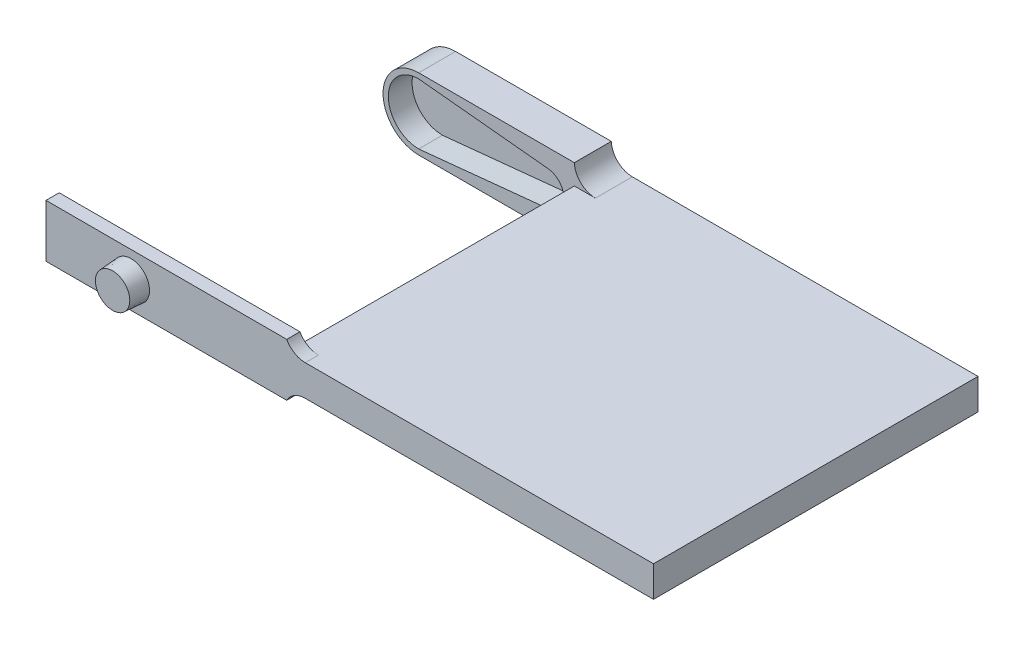
SolidWorks part; units mm, degrees
ref_plane "Front Plane" through (0, 0, 0) normal (0, 0, 1) x (1, 0, 0)
ref_plane "Top Plane" through (0, 0, 0) normal (0, 1, 0) x (1, 0, 0)
ref_plane "Right Plane" through (0, 0, 0) normal (1, 0, 0) x (0, 0, -1)
ref_plane "Ground Plane" through (0, 0, 29.25) normal (0, 0, -1) x (-1, 0, 0)
sketch "Sketch1" plane through (0, 0, 0) normal (0, 0, 1) x (1, 0, 0)
  line L0 (0, 3.375) -> (-13.75, 3.375) construction
  line L1 (0, 3.375) -> (0, 6.25) construction
  line L2 (-12.2651, 5.0167) -> (0, 6.25)
  line L3 (-13.75, 3.375) -> (-13.75, 1.1142) construction
  line L4 (-12.2651, 1.7333) -> (0, 0.5)
  line L5 (12.2651, 1.7333) -> (0, 0.5)
  line L6 (12.2651, 5.0167) -> (0, 6.25)
  line L7 (-2.875, 3.375) -> (-2.875, -5.5898) construction
  line L8 (-14.75, 0) -> (14.75, 0)
  line L9 (-14.75, 0) -> (-14.75, 6.75)
  line L10 (-14.75, 6.75) -> (14.75, 6.75)
  line L11 (-43.5503, 24.4221) -> (7.9447, 11.3967) construction
  line L12 (13.75, 3.375) -> (13.75, 0.9067) construction
  line L13 (14.75, 4.8371) -> (49.5, 4.8371)
  line L14 (14.5, 4.8371) -> (14.5, 1.9129) construction
  line L15 (14.75, 1.9129) -> (49.5, 1.9129)
  line L16 (49.5, 4.8371) -> (49.5, 1.9129)
  line L17 (-43.5503, 24.4221) -> (7.9447, 11.3967)
  line L18 (14.75, 6.75) -> (14.75, 0)
  line L19 (8.1899, 12.3661) -> (3.8863, -4.648) construction
  line L20 (8.1899, 12.3661) -> (3.8863, -4.648)
  line L21 (8.1899, 12.3661) -> (3.8863, -4.648)
  line L22 (8.1899, 12.3661) -> (3.8863, -4.648) construction
  line L23 (8.1899, 12.3661) -> (3.8863, -4.648)
  circle A0 centre (0, 3.375) radius 2.875 construction
  arc A1 (-12.2651, 5.0167) -> (-12.2651, 1.7333) centre (-12.1, 3.375) ccw
  arc A2 (12.2651, 5.0167) -> (12.2651, 1.7333) centre (12.1, 3.375) cw
  circle A3 centre (-12.1, 3.375) radius 0.2914
  circle A4 centre (-10.0632, 3.375) radius 0.2914
  circle A5 centre (-8.0264, 3.375) radius 0.2914
  circle A6 centre (8.0264, 3.375) radius 0.2914
  circle A7 centre (10.0632, 3.375) radius 0.2914
  circle A8 centre (12.1, 3.375) radius 0.2914
  arc A9 (0, 6.75) -> (0, 0) centre (0, 3.375) ccw
  arc A10 (0, 6.25) -> (0, 0.5) centre (0, 3.375) ccw
  point P2 (-14.75, 3.375)
  point P27 (0, 6.75)
  point P34 (14.5, 3.375)
  point P35 (49.5, 3.375)
  dimension "D1" = 5.75
  dimension "D9" = 1.65
  dimension "D3" = 2.9241
  dimension "D5" = 29.5
  dimension "D7" = 6.75
  dimension "D8" = 1.7333
  dimension "D11" = 27.5
  dimension "D6" = 13.75
  dimension "D2" = 3
extrude "Boss-Extrude10" add sketch "Sketch1" along normal blind 3.5 contours L4 A9 L8 L20 L5 | L6 A2 L5 L20 L8 L18 L10 | L10 A9 L2 L6 L20 | A10 L2 A9 L4 region at (3.1883, 6.3261, 0) region at (-1.314, 6.0546, 0) region at (2.2829, 0.3947, 0) region at (10.7597, 6.6319, 0)
extrude "Boss-Extrude15" add sketch "Sketch1<16>" along normal blind 1.25 contours A7 | A8 | L2 A0 L4 L5 L6 | A2 L6 A0 L5 A7 A6 A8 | A6 region at (1.6334, 3.4211, 0) region at (9.4045, 3.3032, 0) region at (10.0632, 3.375, 0) region at (12.1, 3.375, 0)
sketch "Sketch1<16>" plane through (0, 0, 0) normal (0, 0, 1) x (1, 0, 0) same geometry as "Sketch1"
extrude "Boss-Extrude17" add sketch "Sketch1<17>" along direction (0, 0, -1) on the side of the normal offset from surface (30.75 mm away) 1.5 contours L13 L18 L15 L16 region at (32.125, 3.375, 0) offset beyond the face yes
sketch "Sketch1<17>" plane through (0, 0, 0) normal (0, 0, 1) x (1, 0, 0) same geometry as "Sketch1"
sketch "Sketch2" plane through (0, 0, 30.75) normal (0, 0, 1) x (1, 0, 0)
  line L0 (0, 2.75) -> (0, 3.375) construction
  line L1 (13.5, 5.875) -> (-8.0614, 5.875)
  line L3 (14.75, 0.875) -> (-8.0614, 0.875)
  line L4 (-8.0614, 5.875) -> (-8.0614, 0.875)
  line L6 (14.75, 4.8371) -> (14.75, 1.9129) construction
  line L7 (13.5, 5.875) -> (14.75, 5.875)
  line L8 (14.75, 5.875) -> (14.75, 0.875)
  circle A0 centre (0, 3.375) radius 1.75
  circle A3 centre (0, 3.375) radius 2.875 construction
  point P12 (14.5, 3.375)
  dimension "D1" = 3.5
  dimension "D2" = 5
extrude "Boss-Extrude18" add sketch "Sketch2" against normal blind 1.25 contours L1 L4 L3 L8 L7
extrude "Boss-Extrude19" add sketch "Sketch2<9>" along normal blind 1.75 draft 4 contours A0
sketch "Sketch2<9>" plane through (0, 0, 30.75) normal (0, 0, 1) x (1, 0, 0) same geometry as "Sketch2"
fillet "Fillet1" radius 2 4 edges at (14.75, 1.9129, 30.125) (14.75, 4.8371, 30.125)
fillet "Fillet2" [suppressed] radius 4
sketch "Sketch3" [suppressed] plane through (0, 0, 3.5) normal (0, 0, 1) x (1, 0, 0)
  line L0 (-0.1021, 0) -> (-0.1021, 6.75) construction
  line L1 (-2.9771, 6.75) -> (-2.9771, 0) construction
  line L3 (-10.75, 6.75) -> (14.75, 6.75) construction
  line L4 (-14.7009, 3.375) -> (-0.1021, 3.375) construction
  line L5 (2.7729, 6.75) -> (2.7729, 0) construction
  line L6 (2.7729, 6.75) -> (2.7729, 5.625)
  line L7 (-2.9771, 5.625) -> (2.7729, 5.625)
  line L8 (-2.9771, 0) -> (2.7729, 0)
  line L9 (-2.9771, 0) -> (-2.9771, 1.125)
  line L10 (-2.9771, 1.125) -> (2.7729, 1.125)
  line L11 (2.7729, 0) -> (2.7729, 1.125)
  line L12 (-2.9771, 6.75) -> (2.7729, 6.75)
  line L13 (-2.9771, 6.75) -> (-2.9771, 5.625)
  line L19 (-10.75, 0) -> (14.75, 0) construction
  circle A0 centre (-0.1021, 3.375) radius 2.875 construction
  circle A1 centre (-0.1021, 3.375) radius 2.875 construction
  circle A2 centre (-0.1021, 3.375) radius 2.25 construction
  circle A3 centre (-0.1021, 3.375) radius 2.25 construction
extrude "Cut-Extrude1" [suppressed] cut sketch "Sketch3" against normal up to surface (2.25 mm away)
equation "\"D5@Sketch1\"=\"D6@Sketch1\"*2+2"
